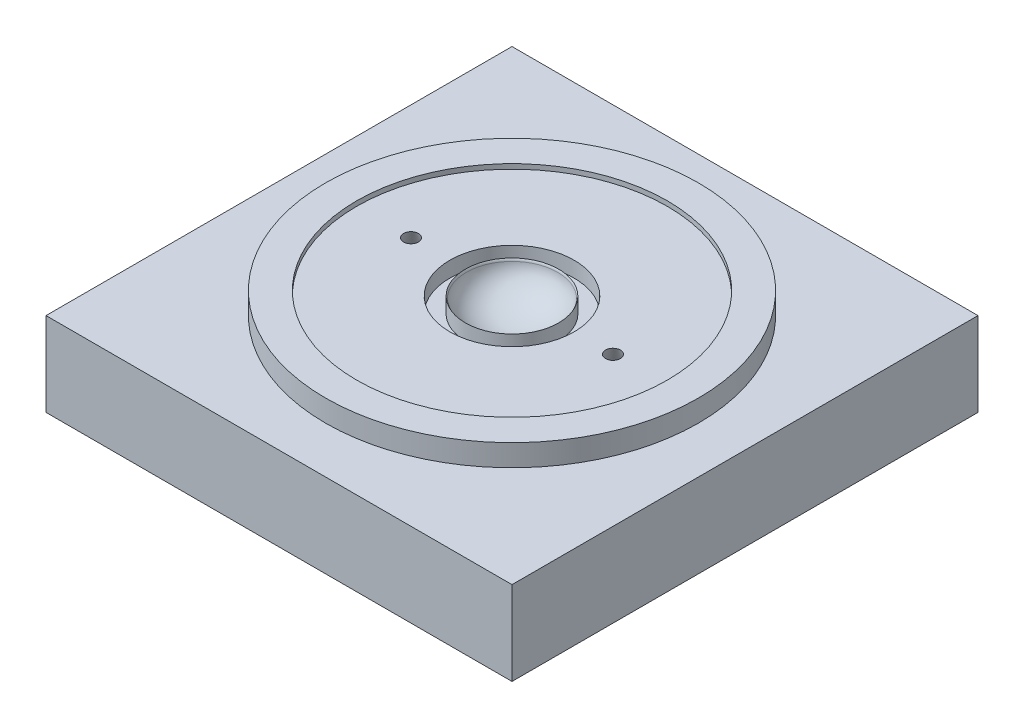
SolidWorks part; units mm, degrees
ref_plane "Front Plane" through (0, 0, 0) normal (0, 0, 1) x (1, 0, 0)
ref_plane "Top Plane" through (0, 0, 0) normal (0, 1, 0) x (1, 0, 0)
ref_plane "Right Plane" through (0, 0, 0) normal (1, 0, 0) x (0, 0, -1)
sketch "Sketch3" plane through (0, 0, 0) normal (0, 1, 0) x (1, 0, 0)
  line L1 (-15, -15) -> (15, -15)
  line L2 (-15, -15) -> (-15, 15)
  line L3 (-15, 15) -> (15, 15)
  line L4 (15, -15) -> (15, 15)
  line L5 (0, 15) -> (0, -15) construction
  line L6 (-15, 0) -> (15, 0) construction
  circle A0 centre (0, 0) radius 12
  circle A1 centre (0, 0) radius 10
  circle A2 centre (0, 0) radius 4
  circle A3 centre (0, 0) radius 3
  point P0 (0, 0)
  dimension "D3" = 24
  dimension "D4" = 20
  dimension "D5" = 8
  dimension "D6" = 6
  dimension "D2" = 30
extrude "Rectangle" add sketch "Sketch3" along normal blind 5.4 contours L1 L4 L3 L2 A0 region at (-14.5757, 0, 0)
extrude "Rim" add sketch "Sketch3<3>" along normal blind 6.8 contours A0 A1 region at (-11.6606, 0, 0)
sketch "Sketch3<3>" plane through (0, 0, 0) normal (0, 1, 0) x (1, 0, 0) same geometry as "Sketch3"
extrude "Flat_face" add sketch "Sketch3<5>" along normal blind 6.49 contours A1 A2 region at (-9.7172, 0, 0)
sketch "Sketch3<5>" plane through (0, 0, 0) normal (0, 1, 0) x (1, 0, 0) same geometry as "Sketch3"
extrude "Gap" add sketch "Sketch3<6>" along normal blind 5.49 contours A2 | A3
sketch "Sketch3<6>" plane through (0, 0, 0) normal (0, 1, 0) x (1, 0, 0) same geometry as "Sketch3"
extrude "Dome_face" add sketch "Sketch3<7>" along normal blind 6.49 contours A3 region at (0, 0, 0)
sketch "Sketch3<7>" plane through (0, 0, 0) normal (0, 1, 0) x (1, 0, 0) same geometry as "Sketch3"
sketch "Sketch5" plane through (0, 6.49, 0) normal (0, 1, 0) x (1, 0, 0)
  circle A0 centre (0, 0) radius 2.95
  dimension "D1" = 5.9
extrude "Dome_primer" cut sketch "Sketch5" against normal blind 0.001
dome "Dome" faces to dome 1 distance 1.95 reverse direction yes elliptical dome yes face at (0, 6.489, 2.95) parameters "D1"=1.95
fillet "Fillet4" radius 0.31 1 edges at (0, 6.49, 2.95)
sketch "Sketch6" plane through (0, 6.49, 0) normal (0, 1, 0) x (1, 0, 0)
  circle A0 centre (-6.5, 0) radius 0.4
  circle A1 centre (6.5, 0) radius 0.4
extrude "Fill-Hole Outer" cut sketch "Sketch6" against normal blind 2.4
sketch "Sketch7" plane through (0, 0, 0) normal (0, -1, 0) x (-1, 0, 0)
  circle A0 centre (-6.5, 0) radius 1.35
  circle A1 centre (6.5, 0) radius 1.35
extrude "Fill-Hole Inner" cut sketch "Sketch7" against normal blind 4.2
chamfer "Fill-Hole Chamfer" distance 2.5 angle 20.81 2 edges at (-6.5, 4.2, -0.4) (6.5, 4.2, -0.4) first distance on face at (-6.5, 6.49, 0.4) first distance on face at (6.5, 6.49, 0.4)
sketch "Sketch8" plane through (0, 0, 0) normal (0, -1, 0) x (1, 0, 0)
  text T0 "ALL_OS_f"
extrude "Label" cut sketch "Sketch8" against normal blind 0.2
equation "\"Rectangle_Height\"= 5.4mm"
equation "\"Rectangle_Width\"= 30mm"
equation "\"Rim_OR\"= 12mm"
equation "\"Hole_OR\"= 4mm"
equation "\"Rim_Oh\"= 1.4mm'Outer height"
equation "\"Thicknss\"= 0.31mm'Parameter #1"
equation "\"Hole_depth\"= 1mm"
equation "\"D2@Sketch3\"= \"Rectangle_Width\""
equation "\"D3@Sketch3\" = \"Rim_OR\" * 2"
equation "\"D5@Sketch3\"= \"Hole_OR\" * 2"
equation "\"D6@Sketch3\" = ( \"Hole_OR\" - 1 ) * 2"
equation "\"D4@Sketch3\" = ( \"Rim_OR\" - 2 ) * 2"
equation "\"D1@Rectangle\"= \"Rectangle_Height\""
equation "\"D1@Rim\"= \"Rectangle_Height\" + \"Rim_Oh\""
equation "\"D1@Flat_face\"= \"Rectangle_Height\" + \"Rim_Oh\" - \"Thicknss\""
equation "\"D1@Gap\" = \"Rectangle_Height\" + \"Rim_Oh\" - \"Thicknss\" - \"Hole_depth\""
equation "\"D1@Dome_face\" = \"Rectangle_Height\" + \"Rim_Oh\" - \"Thicknss\""
equation "\"Dome_depth\"= 1.95mm'Parameter #2"
equation "\"min_width\"= .05mm"
equation "\"D1@Sketch5\"= ( \"Hole_OR\" - 1 - \"min_width\" ) * 2"
equation "\"D1@Dome\"= \"Dome_depth\""
equation "\"D1@Fillet4\"= \"Thicknss\""
